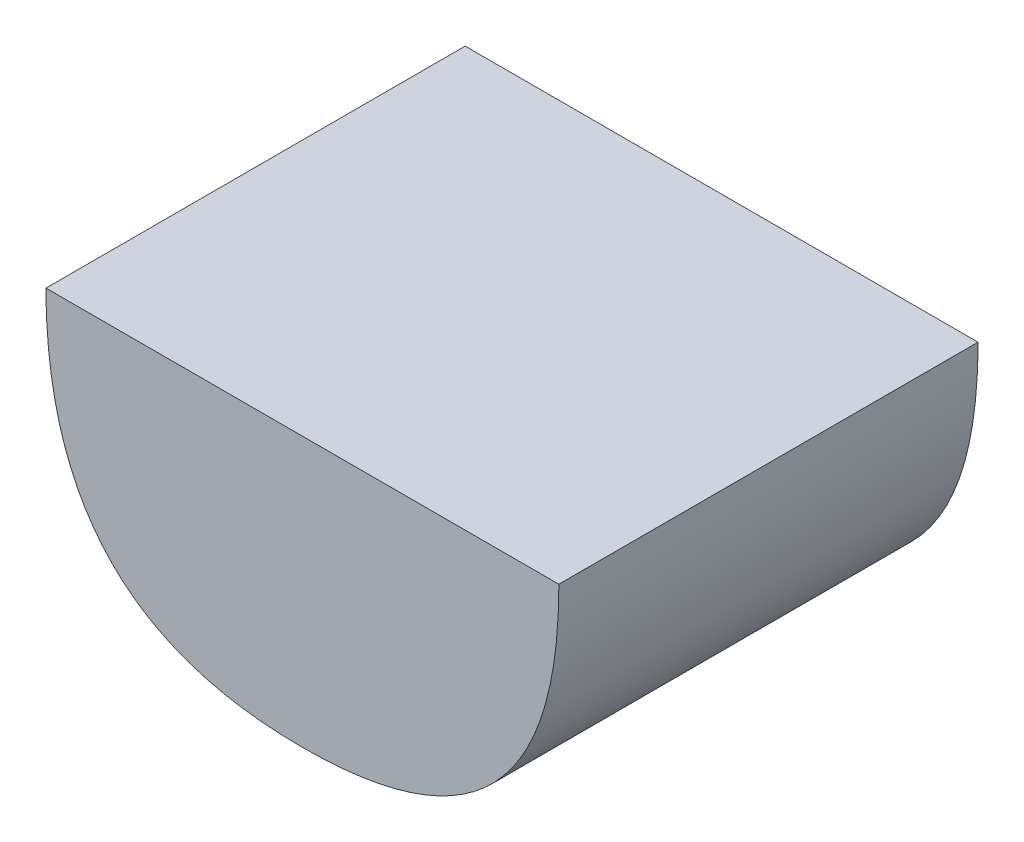
SolidWorks part; units mm, degrees
ref_plane "Front Plane" through (0, 0, 0) normal (0, 0, 1) x (1, 0, 0)
ref_plane "Top Plane" through (0, 0, 0) normal (0, 1, 0) x (1, 0, 0)
ref_plane "Right Plane" through (0, 0, 0) normal (1, 0, 0) x (0, 0, -1)
sketch "Sketch1" plane through (0, 0, 0) normal (0, 0, 1) x (1, 0, 0)
  line L0 (0, 0) -> (0, 317.813) construction
  line L2 (-302.357, 317.813) -> (302.357, 317.813)
  conic Q0 (0, 0) -> (302.357, 317.813) control (302.357, -0.0664) rho 0.504796
  conic Q1 (0, 0) -> (-302.357, 317.813) control (-302.357, -0.0664) rho 0.504796
extrude "Boss-Extrude1" add sketch "Sketch1" against normal blind 247.142 and the other way blind 247.142 contours Q0 L2 Q1
